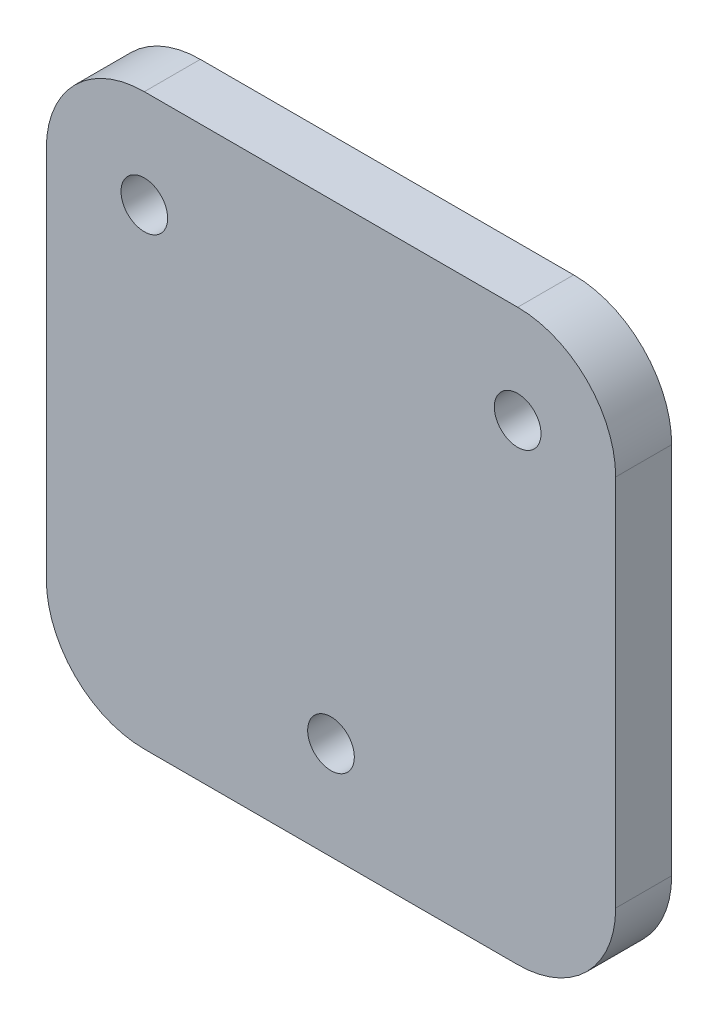
SolidWorks part; units mm, degrees
ref_plane "Plano frontal" through (0, 0, 0) normal (0, 0, 1) x (1, 0, 0)
ref_plane "Plano superior" through (0, 0, 0) normal (0, 1, 0) x (1, 0, 0)
ref_plane "Plano direito" through (0, 0, 0) normal (1, 0, 0) x (0, 0, -1)
sketch "Esboço1" plane through (0, 0, 0) normal (0, 0, 1) x (1, 0, 0)
  line L0 (-20, 30.5) -> (20, 30.5)
  line L1 (-20, 20) -> (20, 20) construction
  line L2 (-20, 20) -> (-20, -20) construction
  line L3 (-20, -20) -> (20, -20) construction
  line L4 (20, 20) -> (20, -20) construction
  line L5 (-20, 20) -> (20, -20) construction
  line L6 (-20, -20) -> (20, 20) construction
  line L9 (30.5, -20) -> (30.5, 20)
  line L10 (20, -30.5) -> (-20, -30.5)
  line L11 (-30.5, -20) -> (-30.5, 20)
  circle A0 centre (-20, 20) radius 2.5
  circle A1 centre (20, 20) radius 2.5
  circle A2 centre (0, -20) radius 2.5
  arc A3 (-20, 30.5) -> (-30.5, 20) centre (-20, 20) ccw
  arc A4 (30.5, 20) -> (20, 30.5) centre (20, 20) ccw
  arc A6 (20, -30.5) -> (30.5, -20) centre (20, -20) ccw
  arc A7 (-30.5, -20) -> (-20, -30.5) centre (-20, -20) ccw
  circle A8 centre (20, 20) radius 10.5 construction
  circle A9 centre (-20, 20) radius 10.5 construction
  point P0 (0, 0)
  point P13 (-8, 22)
  point P14 (0, -20)
  point P15 (32, 22)
  point P18 (12, -22)
  dimension "D3" = 5
  dimension "D1" = 40
  dimension "D2" = 40
  dimension "D4" = 8
extrude "Ressalto-extrusão1" add sketch "Esboço1" along normal blind 6
